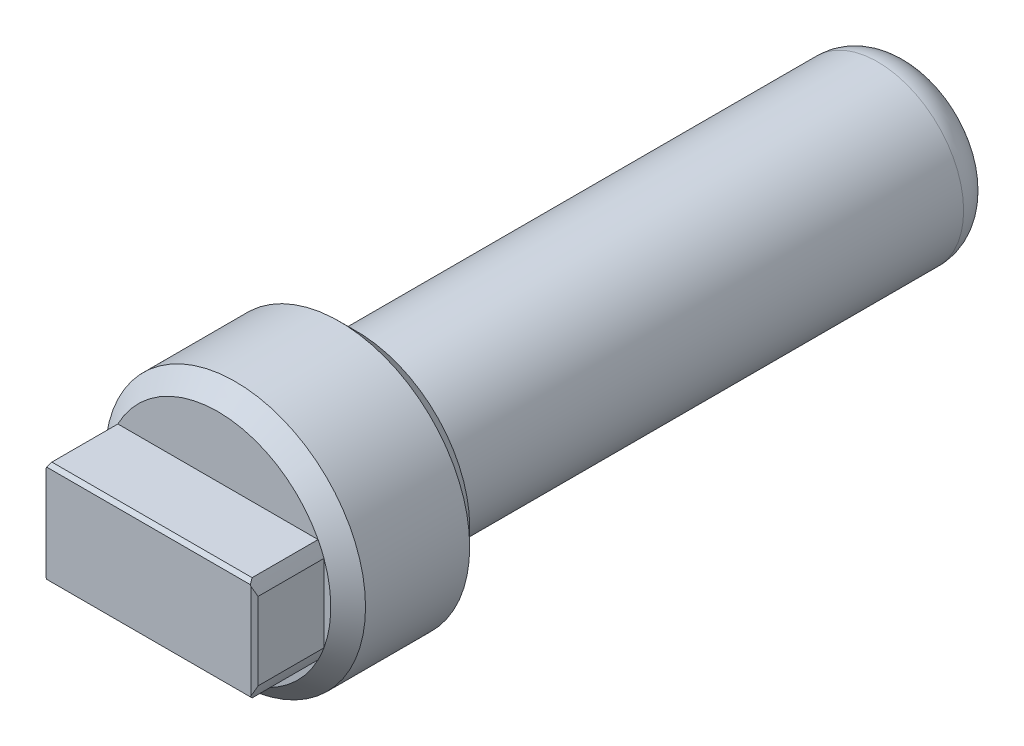
SolidWorks part; units mm, degrees
ref_plane "정면" through (0, 0, 0) normal (0, 0, 1) x (1, 0, 0)
ref_plane "윗면" through (0, 0, 0) normal (0, 1, 0) x (1, 0, 0)
ref_plane "우측면" through (0, 0, 0) normal (1, 0, 0) x (0, 0, -1)
sketch "스케치1" plane through (0, 0, 0) normal (0, 0, 1) x (1, 0, 0)
  circle A0 centre (0, 0) radius 2.475
  dimension "D1" = 4.95
extrude "보스-돌출1" add sketch "스케치1" along normal blind 16
sketch "스케치2" plane through (0, 0, 16) normal (0, 0, 1) x (1, 0, 0)
  circle A0 centre (0, 0) radius 3.75
  dimension "D1" = 7.5
extrude "보스-돌출2" add sketch "스케치2" along normal blind 4
chamfer "모따기1" distance 0.5 angle 45 2 edges at (3.75, 0, 16) (3.75, 0, 20)
sketch "스케치3" plane through (0, 0, 20) normal (0, 0, 1) x (1, 0, 0)
  line L1 (-3.0526, -1.5) -> (3.0526, -1.5)
  line L2 (-3.0526, -1.5) -> (-3.0526, 1.5)
  line L3 (-3.0526, 1.5) -> (3.0526, 1.5)
  line L4 (3.0526, -1.5) -> (3.0526, 1.5)
  line L5 (-3.0526, -1.5) -> (3.0526, 1.5) construction
  line L6 (-3.0526, 1.5) -> (3.0526, -1.5) construction
  circle A0 centre (0, 0) radius 3.4013
  circle M2 centre (0, 0) radius 3.25
  dimension "D1" = 3
extrude "보스-돌출3" add sketch "스케치3" along normal blind 2 contours L4 L3 L2 L1 M2 region at (0, 0, 20)
chamfer "모따기2" distance 0.1 angle 45 4 edges at (3.0526, 0, 22) (-3.0526, 0, 22) (0, -1.5, 22) (0, 1.5, 22)
fillet "필렛1" radius 1 1 edges at (2.475, 0, 0)
